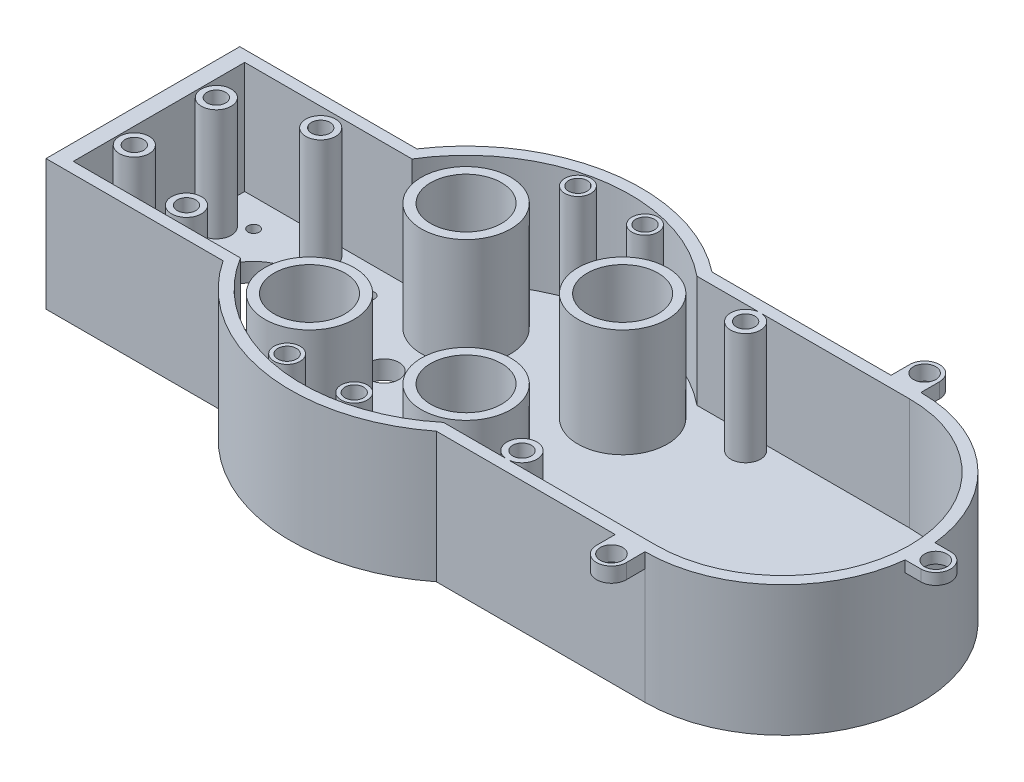
SolidWorks part; units mm, degrees
ref_plane "Front Plane" through (0, 0, 0) normal (0, 0, 1) x (1, 0, 0)
ref_plane "Top Plane" through (0, 0, 0) normal (0, 1, 0) x (1, 0, 0)
ref_plane "Right Plane" through (0, 0, 0) normal (1, 0, 0) x (0, 0, -1)
sketch "Sketch1" plane through (0, 0, 0) normal (0, 1, 0) x (1, 0, 0)
  line L10 (-86.695, 25.9881) -> (-86.695, -25.9919)
  line L15 (-82.3777, 22.9974) -> (-82.3777, -23)
  line L23 (-86.695, 25.9881) -> (-39.195, 25.9881)
  line L24 (-86.695, -25.9919) -> (-39.1892, -25.9919)
  line L28 (-82.3777, 22.9974) -> (-37.5078, 22.9974)
  line L29 (-82.3777, -23) -> (-37.5269, -23)
  line L30 (-21.9899, 0) -> (-57.025, 0)
  line L31 (-57.025, 0) -> (84.9852, 0)
  line L32 (28.9852, 36.9776) -> (84.9852, 37)
  line L33 (28.9852, -36.9776) -> (84.9852, -37)
  line L34 (27.9459, 33.9776) -> (84.9852, 34.0009)
  line L35 (27.9389, -33.9776) -> (84.9852, -34.0009)
  line L36 (-57.025, 0) -> (-86.695, -0.0019)
  circle A1 centre (-20.9904, 20.9904) radius 4.9977
  circle A2 centre (20.9904, 20.9904) radius 4.9977
  circle A3 centre (20.9904, -20.9904) radius 4.9977
  circle A4 centre (-20.9904, -20.9904) radius 4.9977
  circle A5 centre (-21.9899, 0) radius 3.9982
  arc A41 (-39.195, 25.9881) -> (28.9852, 36.9776) centre (-0.0311, 0.0038) cw
  arc A42 (-39.1892, -25.9919) -> (28.9852, -36.9776) centre (-0.0289, -0.0021) ccw
  arc A44 (-37.5269, -23) -> (27.9389, -33.9776) centre (-0.0169, 0) ccw
  arc A45 (-37.5078, 22.9974) -> (27.9459, 33.9776) centre (-0.002, 0) cw
  arc A52 (84.9852, -37) -> (84.9852, 37) centre (85, 0) ccw
  arc A53 (84.9852, 34.0009) -> (84.9852, -34.0009) centre (84.9991, 0) cw
  dimension "D1" = 51.98
  dimension "D2" = 47.5
  dimension "D3" = 47
  dimension "D4" = 47
  dimension "D6" = 37
  dimension "D5" = 56
  dimension "D7" = 29.67
  dimension "D8" = 56
extrude "Boss-Extrude3" add sketch "Sketch1" along normal blind 35 contours A41 L10 A44 L29 L15 region at (-62.945, 0, -23.6992)
extrude "Boss-Extrude4" add sketch "Sketch1<8>" along normal blind 5 separate body contours L29 A44 L15 A5 A4 A3 A2 A1 region at (20.6887, 0, 0.0017)
sketch "Sketch1<8>" plane through (0, 0, 0) normal (0, 1, 0) x (1, 0, 0) same geometry as "Sketch1"
sketch "Sketch2" plane through (0, 5, 0) normal (0, 1, 0) x (1, 0, 0)
  circle A0 centre (-21, 21) radius 9.5
  circle A1 centre (-21, 21) radius 12
  circle A7 centre (-21, -21) radius 9.5
  circle A8 centre (-21, -21) radius 12
  circle A9 centre (21, -21) radius 9.5
  circle A10 centre (21, -21) radius 12
  circle A11 centre (21, 21) radius 9.5
  circle A12 centre (21, 21) radius 12
sketch "Sketch3" plane through (0, 5, 0) normal (0, 1, 0) x (1, 0, 0)
  line L1 (-2.5, -13) -> (-2.5, -8)
  line L2 (-2.5, 13) -> (-2.5, 8)
  line L3 (2.5, 13) -> (2.5, 8)
  line L4 (2.5, -13) -> (2.5, -8)
  arc A2 (-2.5, 13) -> (2.5, 13) centre (0, 13) cw
  arc A3 (-2.5, 8) -> (2.5, 8) centre (0, 8) ccw
  arc A7 (-2.5, -13) -> (2.5, -13) centre (0, -13) ccw
  arc A9 (-2.5, -8) -> (2.5, -8) centre (0, -8) cw
extrude "Cut-Extrude1" cut sketch "Sketch3" against normal blind 10
sketch "Sketch11" plane through (0, 5, 0) normal (0, 1, 0) x (1, 0, 0)
  line L0 (-57, 0.0081) -> (85, 0.0081)
  line L14 (-39.1892, -25.9919) -> (28.9852, -25.9919)
  line L15 (28.9852, -36.9776) -> (28.9852, -20.4283)
  line L18 (-39.195, 25.9881) -> (35.378, 25.9881)
  line L19 (28.9852, 36.9776) -> (28.9852, 25.9881)
  circle A0 centre (-57, 0.0081) radius 11.25
  circle A1 centre (-72.5, 15.5) radius 1.5
  circle A2 centre (-41.5, 15.5) radius 1.5
  circle A3 centre (-41.5, -15.5) radius 1.5
  circle A4 centre (-72.5, -15.5) radius 1.5
  circle A5 centre (85, 0.0081) radius 15
  dimension "D1" = 68.1802
  dimension "D2" = 10.9895
sketch "Sketch22" plane through (0, 35, 0) normal (0, 1, 0) x (1, 0, 0)
  line L0 (-39.195, 25.9881) -> (28.829, 25.9881)
  line L1 (126, 4) -> (121.7831, 4)
  line L2 (126, -4) -> (121.7831, -4)
  line L3 (28.9852, 36.9776) -> (28.829, 25.9881)
  circle A0 centre (126, 0) radius 3
  arc A1 (84.9852, -37) -> (84.9852, 37) centre (85, 0) ccw construction
  arc A2 (126, 4) -> (126, -4) centre (126, 0) cw
  arc M6 (84.9852, -37) -> (84.9852, 37) centre (85, 0) ccw
extrude "Boss-Extrude5" add sketch "Sketch22" against normal blind 3 contours A2 L1 L2 A0 M6 region at (129.8853, 35, 0)
extrude "Boss-Extrude6" add sketch "Sketch2" along normal blind 29
sketch "Sketch23" plane through (0, 35, 0) normal (0, 1, 0) x (1, 0, 0)
  line L0 (85, 37) -> (85, 42)
  line L1 (77, -42) -> (77, -36.9968)
  line L2 (77, 42) -> (77, 36.9968)
  line L3 (28.9852, 36.9776) -> (84.9852, 37) construction
  line L4 (28.9852, -36.9776) -> (84.9852, -37) construction
  line L5 (85, -42) -> (84.9852, -37)
  arc A0 (121.7831, 4) -> (84.9852, 37) centre (85, 0) ccw construction
  circle A1 centre (81, 42) radius 3
  arc A2 (77, 42) -> (85, 42) centre (81, 42) cw
  arc A4 (77, -42) -> (85, -42) centre (81, -42) ccw
  circle A5 centre (81, -42) radius 3
  line M1 (28.9852, -36.9776) -> (84.9852, -37)
  arc M6 (121.7831, 4) -> (84.9852, 37) centre (85, 0) ccw
  line M7 (84.9852, 37) -> (28.9852, 36.9776)
  dimension "D1" = 5.0032
extrude "Boss-Extrude7" add sketch "Sketch23" against normal blind 4 contours L1 A4 L5 A5 M1 | A2 L2 L0 A1 M7 M6 region at (84.9926, 35, -37.1204) region at (77.1204, 35, 39.4984)
extrude "Cut-Extrude2" cut sketch "Sketch11" against normal blind 20 contours A4 | A3 | A0 | A1 | A2 region at (-67.9318, 5, -0.0081) region at (-72.5, 5, -15.5) region at (-41.5, 5, -15.5) region at (-41.5, 5, 15.5) region at (-72.5, 5, 15.5)
sketch "Sketch24" plane through (0, 5, 0) normal (0, 1, 0) x (1, 0, 0)
  circle A0 centre (-78, 11) radius 2.5
  circle A1 centre (-78, -11) radius 2.5
  circle A2 centre (-78, 11) radius 4
  circle A3 centre (-78, -11) radius 4
  circle A4 centre (-57, -18) radius 2.5
  circle A5 centre (-57, -18) radius 4
  circle A6 centre (-57, 18) radius 4
  circle A7 centre (-57, 18) radius 2.5
  circle A11 centre (-9, 39) radius 2.5
  circle A12 centre (-9, 39) radius 3.5
  circle A14 centre (-9, -39) radius 2.5
  circle A15 centre (-9, -39) radius 3.5
  circle A17 centre (9, 39) radius 2.5
  circle A18 centre (9, 39) radius 3.5
  circle A21 centre (9, -39) radius 2.5
  circle A22 centre (9, -39) radius 3.5
  circle A24 centre (45.0005, 29.9881) radius 2.5
  circle A25 centre (45.0005, 29.9881) radius 4
  circle A26 centre (44.9995, -30.0015) radius 2.5
  circle A27 centre (44.9995, -30.0015) radius 4.0096
  line M24 (84.9852, 34.0009) -> (27.9459, 33.9776)
  line M30 (27.9389, -33.9776) -> (84.9852, -34.0009)
  dimension "D2" = 5
  dimension "D3" = 8
  dimension "D1" = 8
extrude "Boss-Extrude8" add sketch "Sketch24" along normal blind 30 contours A3 A1 | A5 A4 | A2 A0 | A6 A7 | A15 A14 | A22 A21 | A18 A17 | A12 A11 | A25 A24 M24 | A27 A26 M30 region at (-81.8869, 5, -11) region at (-81.8869, 5, 11) region at (-60.8869, 5, 18) region at (-60.8869, 5, -18) region at (-12.401, 5, -39) region at (-12.401, 5, 39) region at (5.599, 5, -39) region at (5.599, 5, 39) region at (42.3113, 5, -27.1817) region at (47.9081, 5, 32.5941)
